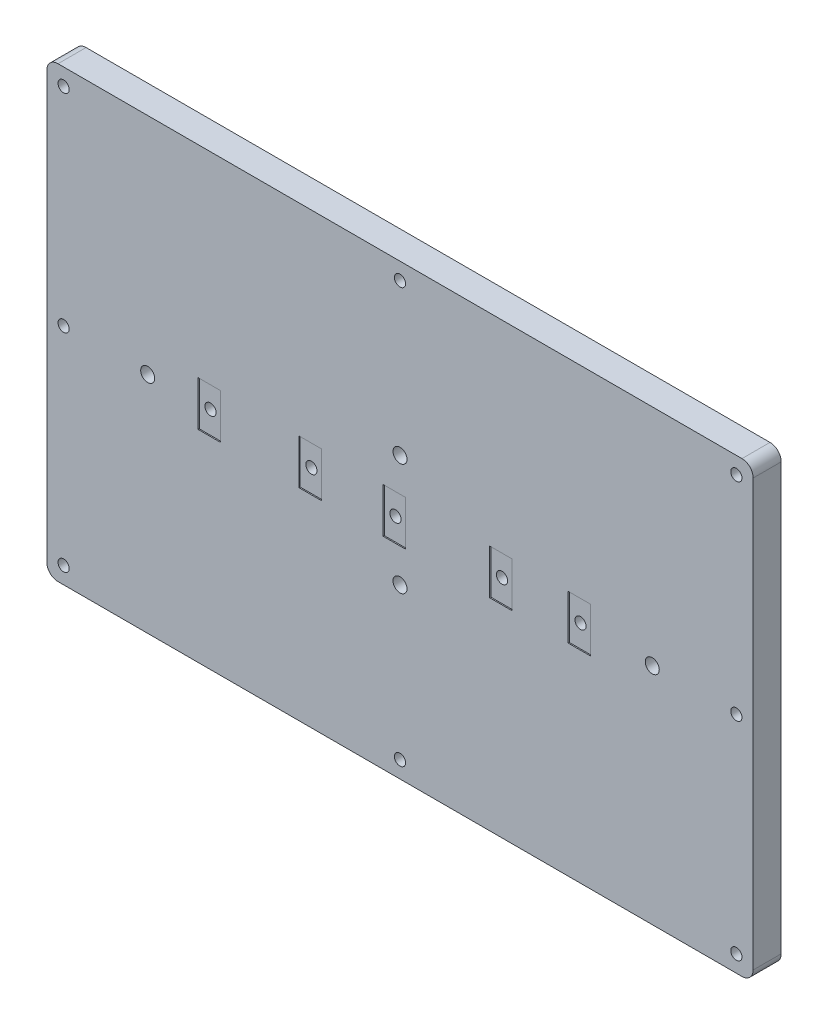
SolidWorks part; units mm, degrees
ref_plane "Front Plane" through (0, 0, 0) normal (0, 0, 1) x (1, 0, 0)
ref_plane "Top Plane" through (0, 0, 0) normal (0, 1, 0) x (1, 0, 0)
ref_plane "Right Plane" through (0, 0, 0) normal (1, 0, 0) x (0, 0, -1)
sketch "Sketch1" plane through (0, 0, 0) normal (0, 0, 1) x (1, 0, 0)
  line L1 (-61, 40) -> (61, 40)
  line L2 (-63, 38) -> (-63, -38)
  line L3 (-61, -40) -> (61, -40)
  line L4 (63, 38) -> (63, -38)
  line L5 (-63, 40) -> (63, -40) construction
  line L6 (-63, -40) -> (63, 40) construction
  arc A0 (61, 40) -> (63, 38) centre (61, 38) cw
  arc A1 (63, -38) -> (61, -40) centre (61, -38) cw
  arc A2 (-61, -40) -> (-63, -38) centre (-61, -38) cw
  arc A3 (-63, 38) -> (-61, 40) centre (-61, 38) cw
  point P0 (0, 0)
  dimension "D1" = 2
sketch "Sketch2" plane through (0, 0, 0) normal (0, 0, 1) x (1, 0, 0)
  line L0 (-5, 5.1169) -> (-5, -5.1169)
  line L1 (-4.2428, -5.5457) -> (4.2854, -0.4287)
  line L2 (4.2854, 0.4287) -> (-4.2428, 5.5457)
  line L3 (-10, -1.5) -> (-10, 1.5)
  line L4 (-10.5, 2) -> (-14, 2)
  line L5 (-14, 2) -> (-14, 5.5)
  line L6 (-14.5, 6) -> (-17.5, 6)
  line L7 (-18, 5.5) -> (-18, 2)
  line L8 (-18, 2) -> (-21.5, 2)
  line L9 (-22, 1.5) -> (-22, -1.5)
  line L10 (-21.5, -2) -> (-18, -2)
  line L11 (-18, -2) -> (-18, -5.5)
  line L12 (-17.5, -6) -> (-14.5, -6)
  line L13 (-14, -5.5) -> (-14, -2)
  line L14 (-14, -2) -> (-10.5, -2)
  line L15 (-28, 1.5) -> (-28, -1.5)
  line L16 (-28.5, -2) -> (-39.5, -2)
  line L17 (-40, -1.5) -> (-40, 1.5)
  line L18 (-39.5, 2) -> (-28.5, 2)
  line L19 (10, 4.5) -> (10, -4.5)
  line L20 (10.5, -5) -> (12.5, -5)
  line L21 (13, -4.5) -> (13, -2)
  line L22 (12.5, 5) -> (10.5, 5)
  line L23 (28, 5.2306) -> (28, -5.2306)
  line L24 (21.2969, 5.6875) -> (13, 2)
  line L25 (13, -2) -> (21.2969, -5.6875)
  line L26 (22, -5.2306) -> (22, 5.2306)
  line L27 (13, 2) -> (13, 4.5)
  line L28 (28.7031, -5.6875) -> (37, -2)
  line L29 (28.7031, 5.6875) -> (37, 2)
  line L30 (37, 2) -> (37, 4.5)
  line L31 (37.5, 5) -> (39.5, 5)
  line L32 (40, 4.5) -> (40, -4.5)
  line L33 (39.5, -5) -> (37.5, -5)
  line L34 (37, -4.5) -> (37, -2)
  arc A0 (-39.5, -2) -> (-40, -1.5) centre (-39.5, -1.5) cw
  arc A1 (-40, 1.5) -> (-39.5, 2) centre (-39.5, 1.5) cw
  arc A2 (-28.5, 2) -> (-28, 1.5) centre (-28.5, 1.5) cw
  arc A3 (-28, -1.5) -> (-28.5, -2) centre (-28.5, -1.5) cw
  arc A4 (-14.5, -6) -> (-14, -5.5) centre (-14.5, -5.5) ccw
  arc A5 (-17.5, -6) -> (-18, -5.5) centre (-17.5, -5.5) cw
  arc A6 (-21.5, -2) -> (-22, -1.5) centre (-21.5, -1.5) cw
  arc A7 (-22, 1.5) -> (-21.5, 2) centre (-21.5, 1.5) cw
  arc A8 (-18, 5.5) -> (-17.5, 6) centre (-17.5, 5.5) cw
  arc A9 (-14.5, 6) -> (-14, 5.5) centre (-14.5, 5.5) cw
  arc A10 (-10.5, 2) -> (-10, 1.5) centre (-10.5, 1.5) cw
  arc A11 (-10.5, -2) -> (-10, -1.5) centre (-10.5, -1.5) ccw
  arc A12 (-4.2428, -5.5457) -> (-5, -5.1169) centre (-4.5, -5.1169) cw
  arc A13 (-5, 5.1169) -> (-4.2428, 5.5457) centre (-4.5, 5.1169) cw
  arc A14 (4.2854, -0.4287) -> (4.2854, 0.4287) centre (4.0282, 0) ccw
  arc A15 (21.2969, 5.6875) -> (22, 5.2306) centre (21.5, 5.2306) cw
  arc A16 (22, -5.2306) -> (21.2969, -5.6875) centre (21.5, -5.2306) cw
  arc A17 (12.5, -5) -> (13, -4.5) centre (12.5, -4.5) ccw
  arc A18 (10.5, -5) -> (10, -4.5) centre (10.5, -4.5) cw
  arc A19 (10, 4.5) -> (10.5, 5) centre (10.5, 4.5) cw
  arc A20 (12.5, 5) -> (13, 4.5) centre (12.5, 4.5) cw
  arc A21 (28.7031, -5.6875) -> (28, -5.2306) centre (28.5, -5.2306) cw
  arc A22 (28, 5.2306) -> (28.7031, 5.6875) centre (28.5, 5.2306) cw
  arc A23 (37.5, -5) -> (37, -4.5) centre (37.5, -4.5) cw
  arc A24 (39.5, -5) -> (40, -4.5) centre (39.5, -4.5) ccw
  arc A25 (37, 4.5) -> (37.5, 5) centre (37.5, 4.5) cw
  arc A26 (40, 4.5) -> (39.5, 5) centre (39.5, 4.5) ccw
  dimension "D1" = 0.5
sketch "Sketch5" plane through (0, 0, 0) normal (0, 0, 1) x (1, 0, 0)
  line L0 (-21, 1) -> (-17, 1)
  line L1 (-39, 1) -> (-29, 1)
  line L2 (-39, 1) -> (-39, -1)
  line L3 (-39, -1) -> (-29, -1)
  line L4 (-29, 1) -> (-29, -1)
  line L5 (-17, 1) -> (-17, 5)
  line L6 (-17, 5) -> (-15, 5)
  line L7 (-15, 5) -> (-15, 1)
  line L8 (-15, 1) -> (-11, 1)
  line L9 (-11, 1) -> (-11, -1)
  line L10 (-11, -1) -> (-15, -1)
  line L11 (-15, -1) -> (-15, -5)
  line L12 (-15, -5) -> (-17, -5)
  line L13 (-17, -5) -> (-17, -1)
  line L14 (-17, -1) -> (-21, -1)
  line L15 (-21, -1) -> (-21, 1)
  line L16 (-4, 4) -> (-4, -4)
  line L17 (-4, -4) -> (3, 0)
  line L18 (3, 0) -> (-4, 4)
  line L19 (29, 4) -> (29, -4)
  line L20 (29, -4) -> (39, 0)
  line L21 (39, 0) -> (29, 4)
  line L22 (11, 0) -> (21, -4)
  line L23 (21, -4) -> (21, 4)
  line L24 (21, 4) -> (11, 0)
extrude "Boss-Extrude1" add sketch "Sketch1" along normal blind 5
extrude "Cut-Extrude1" cut sketch "Sketch2" along normal blind 0.1
ref_plane "Plane2" through (0, 0, 0.5) normal (0, 0, 1) x (1, 0, 0)
sketch "Sketch8" plane through (0, 0, 0.5) normal (0, 0, 1) x (1, 0, 0)
  line L0 (-21, 1) -> (-17, 1)
  line L1 (-39, 1) -> (-29, 1)
  line L2 (-39, 1) -> (-39, -1)
  line L3 (-39, -1) -> (-29, -1)
  line L4 (-29, 1) -> (-29, -1)
  line L5 (-17, 1) -> (-17, 5)
  line L6 (-17, 5) -> (-15, 5)
  line L7 (-15, 5) -> (-15, 1)
  line L8 (-15, 1) -> (-11, 1)
  line L9 (-11, 1) -> (-11, -1)
  line L10 (-11, -1) -> (-15, -1)
  line L11 (-15, -1) -> (-15, -5)
  line L12 (-15, -5) -> (-17, -5)
  line L13 (-17, -5) -> (-17, -1)
  line L14 (-17, -1) -> (-21, -1)
  line L15 (-21, -1) -> (-21, 1)
  line L16 (-4, 4) -> (-4, -4)
  line L17 (-4, -4) -> (3, 0)
  line L18 (3, 0) -> (-4, 4)
  line L19 (29, 4) -> (29, -4)
  line L20 (29, -4) -> (39, 0)
  line L21 (39, 0) -> (29, 4)
  line L22 (11, 0) -> (21, -4)
  line L23 (21, -4) -> (21, 4)
  line L24 (21, 4) -> (11, 0)
  point P21 (0, 0)
ref_plane "Plane3" through (0, 0, 5) normal (0, 0, 1) x (1, 0, 0)
sketch "Sketch9" plane through (0, 0, 5) normal (0, 0, 1) x (1, 0, 0)
  circle A0 centre (-34, 0) radius 1
  circle A1 centre (-16, 0) radius 1
  circle A2 centre (-1, 0) radius 1
  circle A3 centre (18, 0) radius 1
  circle A4 centre (32, 0) radius 1
sketch "Sketch10" plane through (0, 0, 5) normal (0, 0, 1) x (1, 0, 0)
  circle A0 centre (-34, 0) radius 1
  circle A1 centre (-16, 0) radius 1
  circle A2 centre (-1, 0) radius 1
  circle A3 centre (18, 0) radius 1
  circle A4 centre (32, 0) radius 1
extrude "Cut-Extrude2" cut sketch "Sketch10" against normal blind 4.6
sketch "Sketch11" plane through (0, 0, 5) normal (0, 0, 1) x (1, 0, 0)
  line L1 (-36, 4) -> (-32, 4)
  line L2 (-36, 4) -> (-36, -4)
  line L3 (-36, -4) -> (-32, -4)
  line L4 (-32, 4) -> (-32, -4)
  line L5 (-18, 4) -> (-14, 4)
  line L6 (-18, 4) -> (-18, -4)
  line L7 (-18, -4) -> (-14, -4)
  line L8 (-14, 4) -> (-14, -4)
  line L9 (-3, 4) -> (1, 4)
  line L10 (-3, 4) -> (-3, -4)
  line L11 (-3, -4) -> (1, -4)
  line L12 (1, 4) -> (1, -4)
  line L13 (16, 4) -> (20, 4)
  line L14 (16, 4) -> (16, -4)
  line L15 (16, -4) -> (20, -4)
  line L16 (20, 4) -> (20, -4)
  line L17 (30, 4) -> (34, 4)
  line L18 (30, 4) -> (30, -4)
  line L19 (30, -4) -> (34, -4)
  line L20 (34, 4) -> (34, -4)
extrude "Cut-Extrude6" cut sketch "Sketch11" against normal blind 0.2
extrude "Cut-Extrude7" cut sketch "Sketch8" along normal blind 0.2
sketch "Sketch12" plane through (0, 0, 5) normal (0, 0, 1) x (1, 0, 0)
  circle A0 centre (-45, 0) radius 1.25
  circle A1 centre (45, 0) radius 1.25
  circle A2 centre (0, 10) radius 1.25
  circle A3 centre (0, -10) radius 1.25
extrude "Cut-Extrude8" cut sketch "Sketch12" against normal blind 4
sketch "Sketch13" plane through (0, 0, 5) normal (0, 0, 1) x (1, 0, 0)
  circle A0 centre (60, 37) radius 1
  circle A1 centre (60, -37) radius 1
  circle A2 centre (-60, -37) radius 1
  circle A3 centre (-60, 37) radius 1
  circle A4 centre (0, 37) radius 1
  circle A5 centre (0, -37) radius 1
  circle A6 centre (-60, 0) radius 1
  circle A7 centre (60, 0) radius 1
extrude "Cut-Extrude9" cut sketch "Sketch13" against normal blind 5
sketch "Sketch14" plane through (0, 0, 0.5) normal (0, 0, 1) x (1, 0, 0)
  line L0 (-21, 1) -> (-17, 1)
  line L1 (-39, 1) -> (-29, 1)
  line L2 (-39, 1) -> (-39, -1)
  line L3 (-39, -1) -> (-29, -1)
  line L4 (-29, 1) -> (-29, -1)
  line L5 (-17, 1) -> (-17, 5)
  line L6 (-17, 5) -> (-15, 5)
  line L7 (-15, 5) -> (-15, 1)
  line L8 (-15, 1) -> (-11, 1)
  line L9 (-11, 1) -> (-11, -1)
  line L10 (-11, -1) -> (-15, -1)
  line L11 (-15, -1) -> (-15, -5)
  line L12 (-15, -5) -> (-17, -5)
  line L13 (-17, -5) -> (-17, -1)
  line L14 (-17, -1) -> (-21, -1)
  line L15 (-21, -1) -> (-21, 1)
  line L16 (-4, 4) -> (-4, -4)
  line L17 (-4, -4) -> (3, 0)
  line L18 (3, 0) -> (-4, 4)
  line L19 (29, 4) -> (29, -4)
  line L20 (29, -4) -> (39, 0)
  line L21 (39, 0) -> (29, 4)
  line L22 (11, 0) -> (21, -4)
  line L23 (21, -4) -> (21, 4)
  line L24 (21, 4) -> (11, 0)
  point P21 (0, 0)
